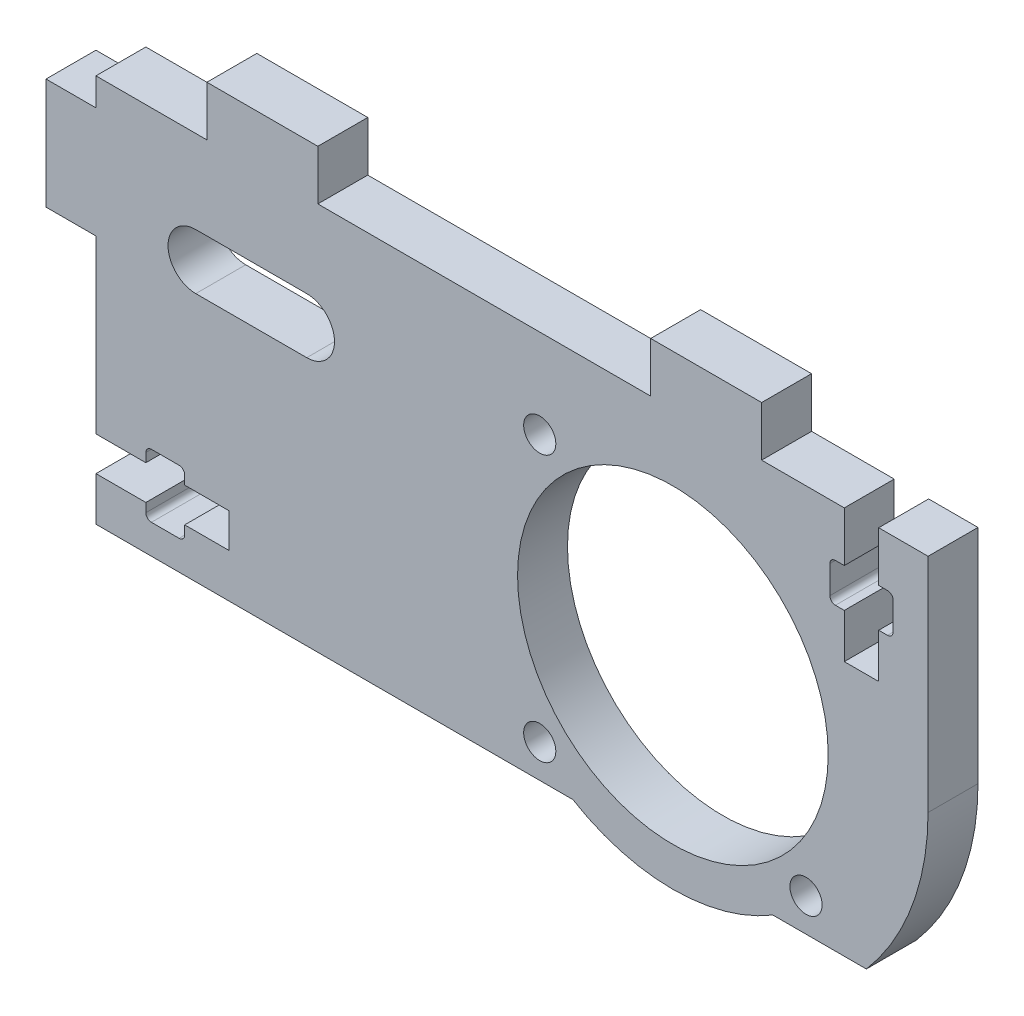
SolidWorks part; units mm, degrees
ref_plane "Front Plane" through (0, 0, 0) normal (0, 0, 1) x (1, 0, 0)
ref_plane "Top Plane" through (0, 0, 0) normal (0, 1, 0) x (1, 0, 0)
ref_plane "Right Plane" through (0, 0, 0) normal (1, 0, 0) x (0, 0, -1)
sketch "Sketch1" plane through (0, 0, 0) normal (0, 0, 1) x (1, 0, 0)
  line L0 (0, 0) -> (0, -35)
  line L1 (0, -35) -> (75, -35)
  line L2 (75, -35) -> (75, 0)
  line L3 (75, 0) -> (0, 0)
  dimension "D1" = 75
  dimension "D2" = 35
extrude "MainShape" add sketch "Sketch1" along normal blind 4.5
sketch "Sketch2" plane through (0, 0, 4.5) normal (0, 0, 1) x (1, 0, 0)
  line L0 (0, -2.5) -> (-4.5, -2.5)
  line L1 (0, 0) -> (0, -35) construction
  line L2 (-4.5, -2.5) -> (-4.5, -12.5)
  line L3 (-4.5, -12.5) -> (0, -12.5)
  line L4 (0, -12.5) -> (0, -2.5)
  line L5 (-4.5, -7.5) -> (0, -7.5) construction
  dimension "D1" = 10
  dimension "D2" = 4.5
  dimension "D3" = 7.5
extrude "RearTab" add sketch "Sketch2" against normal through all
sketch "Sketch3" plane through (0, 0, 4.5) normal (0, 0, 1) x (1, 0, 0)
  line L0 (75, 0) -> (0, 0) construction
  line L1 (10, 0) -> (20, 0)
  line L2 (10, 0) -> (10, 4.5)
  line L3 (10, 4.5) -> (20, 4.5)
  line L4 (20, 0) -> (20, 4.5)
  line L5 (15, 4.5) -> (15, 0) construction
  line L6 (50, 0) -> (60, 0)
  line L7 (50, 0) -> (50, 4.5)
  line L8 (50, 4.5) -> (60, 4.5)
  line L9 (60, 0) -> (60, 4.5)
  line L10 (55, 4.5) -> (55, 0) construction
  dimension "D1" = 4.5
  dimension "D2" = 10
  dimension "D3" = 40
  dimension "D4" = 15
extrude "Boss-Extrude3" add sketch "Sketch3" against normal through all
sketch "Sketch4" plane through (0, 0, 4.5) normal (0, 0, 1) x (1, 0, 0)
  line L0 (69, 0) -> (69, -12) construction
  line L1 (75, 0) -> (60, 0) construction
  line L2 (70.55, -12) -> (67.45, -12) construction
  line L3 (67.45, -12) -> (67.45, 0) construction
  line L4 (67.45, 0) -> (67.45, -4.5)
  line L5 (67.45, -4.5) -> (66.65, -4.5)
  line L6 (66.15, -5) -> (66.15, -7.5)
  line L7 (66.65, -8) -> (67.45, -8)
  line L8 (67.45, -8) -> (67.45, -12)
  line L9 (67.45, -12) -> (70.55, -12)
  line L10 (67.45, 0) -> (70.55, 0)
  line L11 (70.55, -12) -> (70.55, 0) construction
  line L12 (70.55, -8) -> (70.55, -12)
  line L13 (71.35, -8) -> (70.55, -8)
  line L14 (71.85, -5) -> (71.85, -7.5)
  line L15 (70.55, -4.5) -> (71.35, -4.5)
  line L16 (70.55, 0) -> (70.55, -4.5)
  arc A0 (66.15, -7.5) -> (66.65, -8) centre (66.65, -7.5) ccw
  arc A1 (66.65, -4.5) -> (66.15, -5) centre (66.65, -5) ccw
  arc A2 (71.35, -4.5) -> (71.85, -5) centre (71.35, -5) cw
  arc A3 (71.85, -7.5) -> (71.35, -8) centre (71.35, -7.5) cw
  point P13 (66.15, -8)
  point P16 (66.15, -4.5)
  point P27 (71.85, -4.5)
  point P28 (71.85, -8)
  dimension "D7" = 0.5
  dimension "D1" = 12
  dimension "D2" = 1.55
  dimension "D3" = 3.5
  dimension "D4" = 2.85
  dimension "D5" = 8
  dimension "D6" = 69
extrude "Cut-Extrude1" cut sketch "Sketch4" against normal through all
sketch "Sketch5" plane through (0, 0, 4.5) normal (0, 0, 1) x (1, 0, 0)
  line L0 (45.0208, 0) -> (45.0208, 4.5) construction
  line L1 (42.5416, 0) -> (47.5, 0)
  line L2 (42.5416, 0) -> (42.5416, -5.18)
  line L3 (42.5416, -5.18) -> (47.5, -5.18)
  line L4 (47.5, 0) -> (47.5, -5.18)
  line L5 (42.5416, 0) -> (47.5, -5.18) construction
  line L6 (42.5416, -5.18) -> (47.5, 0) construction
  line L7 (42, -4.18) -> (48, -4.18) construction
  line L8 (50, 0) -> (20, 0) construction
  line L9 (48, -4.18) -> (48, -1.18) construction
  line L10 (48, -2.68) -> (58, -2.68) construction
  line L11 (48, -4.18) -> (48, -1.18) construction
  line L12 (58, -1.18) -> (58, -4.18) construction
  line L13 (53, -2.68) -> (53, 0) construction
  line L14 (5, 0) -> (37.5, 0) construction
  line L15 (63.4584, -5.18) -> (58.5, 0) construction
  line L16 (63.4584, 0) -> (58.5, -5.18) construction
  line L17 (58.5, 0) -> (58.5, -5.18)
  line L18 (63.4584, -5.18) -> (58.5, -5.18)
  line L19 (63.4584, 0) -> (63.4584, -5.18)
  line L20 (63.4584, 0) -> (58.5, 0)
  line L21 (42.5416, -5.18) -> (47.5, 0) construction
  point P0 (45.0208, -2.59)
  point P27 (60.9792, -2.59)
  dimension "D1" = 1
  dimension "D2" = 0
  dimension "D3" = 0.5
extrude "Cut-Extrude2" [suppressed] cut sketch "Sketch5" against normal through all
sketch "Sketch6" plane through (0, 0, 4.5) normal (0, 0, 1) x (1, 0, 0)
  line L0 (52, -20) -> (40, -8) construction
  line L2 (52, -34) -> (52, -6) construction
  line L3 (52, -20) -> (38, -20) construction
  line L4 (52, -20) -> (64, -8) construction
  line L5 (52, -20) -> (64, -32) construction
  line L6 (52, -20) -> (40, -32) construction
  circle A0 centre (52, -20) radius 14
  circle A1 centre (40, -8) radius 1.45
  circle A3 centre (64, -32) radius 1.45
  circle A4 centre (40, -32) radius 1.45
  dimension "D1" = 28
  dimension "D4" = 2.9
  dimension "D2" = 52
  dimension "D3" = 20
  dimension "D5" = 12
  dimension "D6" = 45
extrude "Cut-Extrude3" cut sketch "Sketch6" against normal through all
sketch "Sketch7" plane through (0, 0, 4.5) normal (0, 0, 1) x (1, 0, 0)
  line L0 (0, -35) -> (61.0139, -35)
  arc A0 (42.9861, -35) -> (61.0139, -35) centre (52, -20) ccw
  circle A1 centre (52, -20) radius 14 construction
  dimension "D1" = 17.5
extrude "Boss-Extrude4" add sketch "Sketch7" against normal through all contours L0 A0 region at (52, -36.0064, 4.5)
sketch "Sketch8" [suppressed] plane through (0, 0, 4.5) normal (0, 0, 1) x (1, 0, 0)
  line L1 (0, -35) -> (39.1367, -35) construction
  line L18 (15, -35) -> (15, -9.316) construction
  line L19 (6.3379, -28.8128) -> (15, -37.4749) construction
  line L20 (8.8128, -26.3379) -> (17.4749, -35) construction
  line L21 (6.3379, -28.8128) -> (8.8128, -26.3379) construction
  line L22 (15, -35) -> (7.5754, -27.5754) construction
  line L23 (15, -37.4749) -> (11.0756, -33.5504)
  line L24 (11.0756, -33.5504) -> (10.1917, -34.4343)
  line L25 (10.1917, -34.4343) -> (7.2218, -31.4645)
  line L26 (7.2218, -31.4645) -> (8.1057, -30.5806)
  line L27 (8.1057, -30.5806) -> (6.3379, -28.8128)
  line L28 (15, -37.4749) -> (15, -35)
  line L29 (17.4749, -35) -> (15, -35)
  line L30 (8.8128, -26.3379) -> (6.3379, -28.8128)
  line L31 (10.5806, -28.1057) -> (8.8128, -26.3379)
  line L32 (11.4645, -27.2218) -> (10.5806, -28.1057)
  line L33 (14.4343, -30.1917) -> (11.4645, -27.2218)
  line L34 (13.5504, -31.0756) -> (14.4343, -30.1917)
  line L35 (17.4749, -35) -> (13.5504, -31.0756)
  dimension "D7" = 15
extrude "Cut-Extrude4" [suppressed] cut sketch "Sketch8" against normal through all
sketch "Sketch10" [suppressed] plane through (0, 0, 4.5) normal (0, 0, 1) x (1, 0, 0)
  line L0 (17.4749, -35) -> (21.7175, -30.7574)
  line L1 (21.7175, -30.7574) -> (25.253, -34.2929)
  line L2 (25.253, -34.2929) -> (24.5459, -35)
  line L3 (17.4749, -35) -> (39.1367, -35) construction
  line L4 (24.5459, -35) -> (17.4749, -35)
  line L5 (17.4749, -35) -> (13.5504, -31.0756) construction
  dimension "D1" = 5
  dimension "D2" = 6
extrude "Cut-Extrude6" [suppressed] cut sketch "Sketch10" against normal through all
sketch "Sketch12" plane through (0, 0, 4.5) normal (0, 0, 1) x (1, 0, 0)
  line L0 (7.3224, -34.6526) -> (32.3224, -34.6526) construction
  circle A0 centre (32.3224, -34.6526) radius 5
  circle A1 centre (7.3224, -34.6526) radius 5
  dimension "D1" = 10
  dimension "D2" = 10
  dimension "D3" = 25
  dimension "D4" = 34.6526
  dimension "D5" = 7.3224
extrude "Boss-Extrude5" [suppressed] add sketch "Sketch12" against normal through all
sketch "Sketch11" plane through (0, 0, 4.5) normal (0, 0, 1) x (1, 0, 0)
  line L0 (0, -29.5) -> (12, -29.5) construction
  line L1 (0, -12.5) -> (0, -35) construction
  line L2 (12, -31.05) -> (12, -27.95) construction
  line L3 (12, -27.95) -> (0, -27.95) construction
  line L4 (0, -31.05) -> (0, -27.95)
  line L5 (0, -27.95) -> (4.5, -27.95)
  line L6 (4.5, -27.95) -> (4.5, -27.15)
  line L7 (5, -26.65) -> (7.5, -26.65)
  line L8 (8, -27.15) -> (8, -27.95)
  line L9 (8, -27.95) -> (12, -27.95)
  line L10 (12, -27.95) -> (12, -31.05)
  line L11 (12, -31.05) -> (0, -31.05) construction
  line L12 (8, -31.05) -> (12, -31.05)
  line L13 (8, -31.85) -> (8, -31.05)
  line L14 (5, -32.35) -> (7.5, -32.35)
  line L15 (4.5, -31.05) -> (4.5, -31.85)
  line L16 (0, -31.05) -> (4.5, -31.05)
  line L17 (-4.5, -2.5) -> (-4.5, -12.5) construction
  arc A0 (7.5, -26.65) -> (8, -27.15) centre (7.5, -27.15) cw
  arc A1 (4.5, -27.15) -> (5, -26.65) centre (5, -27.15) cw
  arc A2 (4.5, -31.85) -> (5, -32.35) centre (5, -31.85) ccw
  arc A3 (7.5, -32.35) -> (8, -31.85) centre (7.5, -31.85) ccw
  point P12 (8, -26.65)
  point P15 (4.5, -26.65)
  point P26 (4.5, -32.35)
  point P27 (8, -32.35)
  point P28 (-4.5, -7.5)
  dimension "D1" = 12
  dimension "D2" = 1.55
  dimension "D3" = 3.5
  dimension "D4" = 2.85
  dimension "D5" = 8
  dimension "D6" = 0.5
  dimension "D7" = 22
extrude "Cut-Extrude7" cut sketch "Sketch11" against normal through all
sketch "Sketch13" [suppressed] plane through (0, 0, 4.5) normal (0, 0, 1) x (1, 0, 0)
  circle A0 centre (7.3224, -34.6526) radius 1.45
  circle A1 centre (32.3224, -34.6526) radius 1.45
  arc A2 (2.3345, -35) -> (12.3103, -35) centre (7.3224, -34.6526) ccw construction
  arc A3 (27.3345, -35) -> (37.3103, -35) centre (32.3224, -34.6526) ccw construction
  dimension "D1" = 2.9
extrude "Cut-Extrude8" [suppressed] cut sketch "Sketch13" against normal through all
sketch "Sketch14" plane through (0, 0, 4.5) normal (0, 0, 1) x (1, 0, 0)
  line L0 (75, -35) -> (75, 0) construction
  line L1 (69.4356, -35) -> (75, -35)
  line L2 (75, -35) -> (75, -20)
  arc A0 (69.4356, -35) -> (75, -20) centre (52, -20) ccw
  circle A1 centre (52, -20) radius 14 construction
extrude "SmoothEdge" cut sketch "Sketch14" against normal through all
sketch "Sketch15" plane through (0, 0, 4.5) normal (0, 0, 1) x (1, 0, 0)
  line L0 (30, -27) -> (30, -8)
  line L1 (30, -8) -> (8, -8)
  line L2 (8, -8) -> (30, -27)
  line L3 (50, 0) -> (20, 0) construction
  line L4 (0, -35) -> (42.9861, -35) construction
  line L5 (0, -12.5) -> (0, -27.95) construction
  line L6 (38, -20) -> (38, -36.8214) construction
  circle A1 centre (52, -20) radius 14 construction
  dimension "D1" = 8
  dimension "D2" = 8
  dimension "D3" = 8
  dimension "D4" = 8
extrude "Cut-Extrude9" [suppressed] cut sketch "Sketch15" against normal through all
sketch "Sketch16" plane through (0, 0, 4.5) normal (0, 0, 1) x (1, 0, 0)
  line L0 (6, -6) -> (37.7171, -6)
  line L1 (6, -6) -> (6, -19.95)
  line L2 (6, -19.95) -> (15.8505, -19.95)
  line L3 (12, -27.95) -> (8, -27.95) construction
  line L4 (15.8505, -19.95) -> (32.0001, -19.95)
  line L5 (0, -12.5) -> (0, -27.95) construction
  line L6 (50, 0) -> (20, 0) construction
  arc A0 (37.7171, -6) -> (32.0001, -19.95) centre (52, -20) ccw
  circle A1 centre (52, -20) radius 14 construction
  dimension "D3" = 6
  dimension "D1" = 6
  dimension "D2" = 6
  dimension "D4" = 8
extrude "Cut-Extrude10" [suppressed] cut sketch "Sketch16" against normal through all
sketch "Sketch17" plane through (0, 0, 4.5) normal (0, 0, 1) x (1, 0, 0)
  line L0 (9, -10) -> (19, -10) construction
  line L1 (9, -7.5) -> (19, -7.5)
  line L2 (9, -12.5) -> (19, -12.5)
  arc A0 (9, -7.5) -> (9, -12.5) centre (9, -10) ccw
  arc A1 (19, -12.5) -> (19, -7.5) centre (19, -10) ccw
  point P2 (14, -10)
  dimension "D1" = 5
  dimension "D2" = 10
  dimension "D3" = 14
  dimension "D4" = 10
extrude "Cut-Extrude11" cut sketch "Sketch17" against normal through all
equation "\"X-ROD-SPACING\"=45"
equation "\"Y-ROD-SPACING\"=75"
equation "\"Z-ROD-SPACING\"=17.5"
equation "\"Y-BED-OFFSET\"=2"
equation "\"Y-BED-ROD-INSET\"=3.5"
equation "\"Y-BED-SCREW-SPACING\"=209"
equation "\"Y-BED-SCREW-CUTOUT-SLOT-HEIGHT\"=2"
equation "\"T-SLOT-NUT-FILLET-RADIUS\"=0.5"
equation "\"T-SLOT-SCREW-SHAFT-RADIUS\"=1.55"
equation "\"T-SLOT-SCREW-SHAFT-CUTOUT-LENGTH\"=11"
equation "\"T-SLOT-NUT-DEPTH\"=3.5"
equation "\"T-SLOT-NUT-WIDTH\"=2.85"
equation "\"T-SLOT-NUT-END-DISTANCE\"=8"
equation "\"ACRYLIC-THICKNESS\"=10"
equation "\"ACRYLIC-THICKNESS2\"=4.5"
equation "\"ACRYLIC-TAB-CUTOUT-SIZE\"=\"ACRYLIC-THICKNESS\"+\"ACRYLIC-TAB-TOLERANCE\"*2"
equation "\"ACRYLIC-TAB-TOLERANCE\"=-.05"
equation "\"ACRYLIC-TAB-WIDTH\"=\"ACRYLIC-THICKNESS\""
equation "\"ACRYLIC-M3-HOLE\"=2.9"
equation "\"SMOOTHROD-CAP-SCREW-DISTANCE\"=20"
equation "\"FRAME-WIDTH-INNER\"=370"
equation "\"NEMA17-HOLE-SPACING\"=31"
equation "\"NEMA17-CENTRAL-CUTOUT\"=22.5"
equation "\"Z-BRACKET-REACH\"=57"
equation "\"Z-ROD-INSET\"=13.5"
equation "\"TOP-BRACKET-SPACING\"=40"
equation "\"SMOOTHROD-X-LENGTH\"=350"
equation "\"SMOOTHROD-Y-LENGTH\"=350"
equation "\"SMOOTHROD-Z-LENGTH\"=350"
equation "\"SMOOTHROD-TIGHTENING-HEADROOM\"=.25"
equation "\"LEADSCREW-Z-LENGTH\"=300"
equation "\"SCREW-LENGTH-FRAME\"=\"ACRYLIC-THICKNESS\" + 10"
equation "\"SCREW-LENGTH-MOTOR\"=\"ACRYLIC-THICKNESS\" + 5"
equation "\"SCREW-LENGTH-EXTRUDER\"=28"
equation "\"SCREW-HEAD-RADIUS\"=6"
equation "\"PRINTED-M3-HOLE\"=3.5"
equation "\"PRINTED-X-SMOOTHROD-DIAMETER\"=8.8"
equation "\"PRINTED-X-SMOOTHROD-CUTOUT\"=10"
equation "\"PRINTED-X-BASE-HEIGHT\"=10"
equation "\"PRINTED-LM8UU-CUTOUT-SIZE\"=15.5"
equation "\"PRINTED-LM8UU-CUTOUT-LENGTH\"=24.5"
equation "\"PRINTED-X-IDLER-HEIGHT\"=16"
equation "\"PRINTED-M3-NUT-AF\"=6.25"
equation "\"PSU-MOUNTING-WIDTH\"=95"
equation "\"PSU-MOUNTING-HEIGHT\"=177"
equation "\"Y-BELT-TO-ROD-DISTANCE\"=20"
equation "\"SPOOL-HOLDER-ROD-SPACING\"=150"
equation "\"ACRYLIC-X-CARRIAGE-WIDTH\"=55"
equation "\"ACRYLIC-X-CARRIAGE-HEIGHT\"=75"
equation "\"ACRYLIC-X-CARRIAGE-LM8UU-CUTOUT-WIDTH\"=24.25"
equation "\"ACRYLIC-X-CARRIAGE-LM8UU-CUTOUT-HEIGHT\"=11.0"
equation "\"ACRYLIC-X-CARRIAGE-SCREW-SPACING-X\"=15"
equation "\"ACRYLIC-X-CARRIAGE-SCREW-SPACING-Y\"=33"
equation "\"ACRYLIC-X-CARRIAGE-CENTER-TAB-SPACING\"=14"
equation "\"ACRYLIC-X-CARRIAGE-EXTRUDER-OFFSET\"=26"
equation "\"ACRYLIC-X-CARRIAGE-EXTRUDER-ANGLE\"=90"
equation "\"ACRYLIC-X-CARRIAGE-EXTRUDER-SHELF-DEPTH\"=\"ACRYLIC-X-CARRIAGE-EXTRUDER-OFFSET\" + 28"
equation "\"ACRYLIC-X-CARRIAGE-EXTRUDER-BRACE-SPACING\"=23"
equation "\"ACRYLIC-X-CARRIAGE-EXTRUDER-BRACE-TAB-OFFSET\"=20"
equation "\"ACRYLIC-X-CARRIAGE-EXTRUDER-BRACE-HEIGHT\"=35"
equation "\"ACRYLIC-X-CARRIAGE-EXTRUDER-BRACE-SCREW-SPACING\"=22"
equation "\"ACRYLIC-X-CARRIAGE-DUAL-WIDTH-MULTIPLIER\"=1.65"
equation "\"ACRYLIC-X-CARRIAGE-DUAL-HOTEND-SPACING\"=42"
equation "\"ACRYLIC-X-CARRIAGE-DUAL-WIDTH\"=75"
equation "\"ACRYLIC-X-CARRIAGE-DUAL-FAN-OFFSET\"=52"
equation "\"ACRYLIC-X-CARRIAGE-DUAL-FAN-HEIGHT\"=20"
equation "\"ACRYLIC-X-CARRIAGE-DUAL-HOTEND-SEPARATION\"=36"
equation "\"ACRYLIC-X-CARRIAGE-DUAL-MOUNT-PLATE-DEPTH\"=75"
equation "\"ACRYLIC-X-CARRIAGE-DUAL-MOUNT-BRACE-WIDTH\"=33"
equation "\"ACRYLIC-X-CARRIAGE-DUAL-MOUNT-SCREW-WIDTH\"=40"
equation "\"BLOWER-FAN-WIDTH\"=15"
equation "\"D1@Sketch1\"=\"ACRYLIC-X-CARRIAGE-DUAL-MOUNT-PLATE-DEPTH\""
equation "\"D2@Sketch1\"=\"ACRYLIC-X-CARRIAGE-EXTRUDER-BRACE-HEIGHT\""
equation "\"D1@MainShape\" = \"ACRYLIC-THICKNESS2\""
equation "\"D1@Sketch2\"=\"ACRYLIC-TAB-WIDTH\""
equation "\"D2@Sketch2\"=\"ACRYLIC-THICKNESS2\""
equation "\"D1@Sketch3\"=\"ACRYLIC-THICKNESS2\""
equation "\"D2@Sketch3\"=\"ACRYLIC-TAB-WIDTH\""
equation "\"D1@Sketch4\"=\"T-SLOT-SCREW-SHAFT-CUTOUT-LENGTH\"+1"
equation "\"D2@Sketch4\"=\"T-SLOT-SCREW-SHAFT-RADIUS\""
equation "\"D3@Sketch4\"=\"T-SLOT-NUT-DEPTH\""
equation "\"D4@Sketch4\"=\"T-SLOT-NUT-WIDTH\""
equation "\"D5@Sketch4\"=\"T-SLOT-NUT-END-DISTANCE\""
equation "\"D7@Sketch4\"=\"T-SLOT-NUT-FILLET-RADIUS\""
equation "\"D2@Sketch6\"=\"ACRYLIC-X-CARRIAGE-DUAL-FAN-OFFSET\""
equation "\"D3@Sketch6\"=\"ACRYLIC-X-CARRIAGE-DUAL-FAN-HEIGHT\""
equation "\"D4@Sketch6\"=\"ACRYLIC-M3-HOLE\""
equation "\"D1@Sketch11\"=\"T-SLOT-SCREW-SHAFT-CUTOUT-LENGTH\"+1"
equation "\"D2@Sketch11\"=\"T-SLOT-SCREW-SHAFT-RADIUS\""
equation "\"D3@Sketch11\"=\"T-SLOT-NUT-DEPTH\""
equation "\"D4@Sketch11\"=\"T-SLOT-NUT-WIDTH\""
equation "\"D5@Sketch11\"=\"T-SLOT-NUT-END-DISTANCE\""
equation "\"D6@Sketch11\"=\"T-SLOT-NUT-FILLET-RADIUS\""
equation "\"D1@Sketch13\"=\"ACRYLIC-M3-HOLE\""
